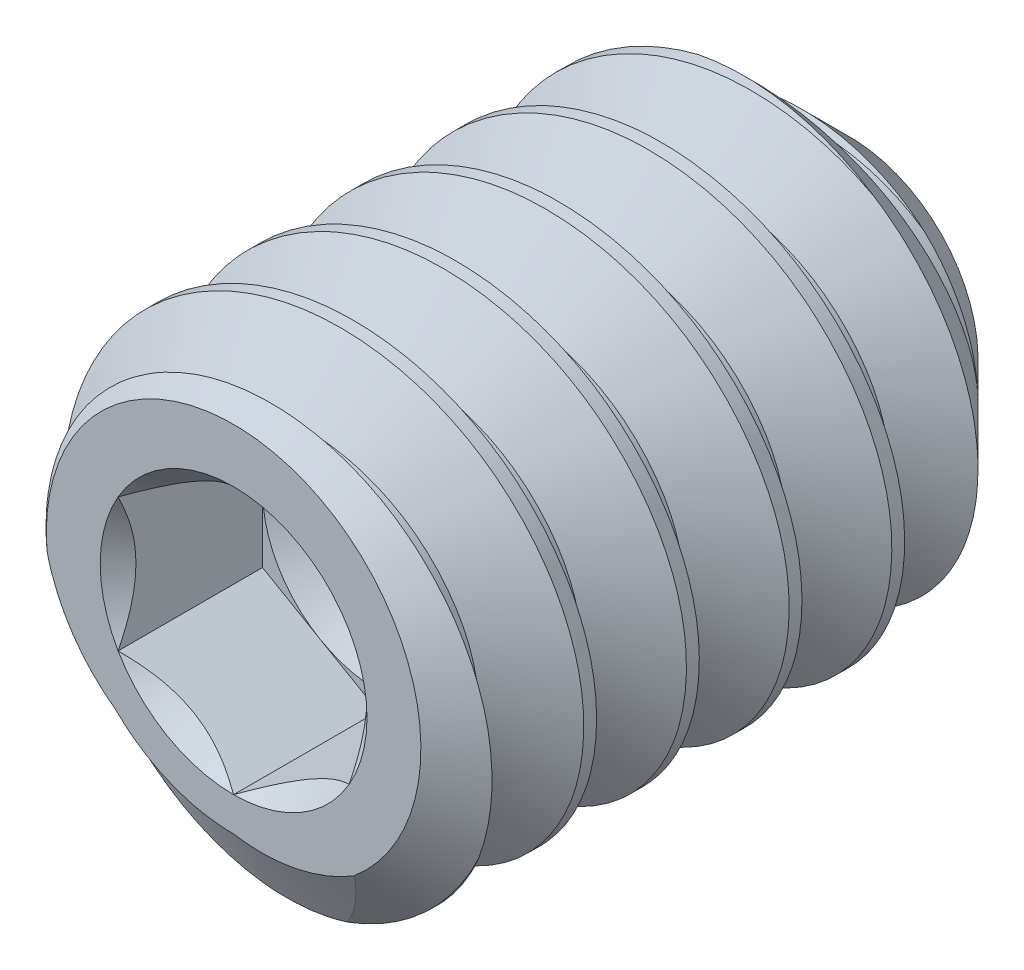
SolidWorks part; units mm, degrees
ref_plane "Front" through (0, 0, 0) normal (0, 0, 1) x (1, 0, 0)
ref_plane "Top" through (0, 0, 0) normal (0, 1, 0) x (1, 0, 0)
ref_plane "Right" through (0, 0, 0) normal (1, 0, 0) x (0, 0, -1)
sketch "Sketch22" plane through (0, 0, 0) normal (1, 0, 0) x (0, 0, -1)
  line L0 (-2.7778, 0) -> (-2.7778, 1.9304)
  line L1 (-2.7778, 1.9304) -> (-2.4398, 2.413)
  line L2 (-2.4398, 2.413) -> (2.4815, 2.413)
  line L3 (2.4815, 2.413) -> (3.5722, 1.3222)
  line L4 (3.5722, 1.3222) -> (2.7778, 0) construction
  line L5 (2.7778, 0) -> (-2.7778, 0)
  line L6 (2.7778, 0) -> (3.5722, 0) construction
  line L7 (3.5722, 0) -> (3.5722, 1.3222) construction
  line L8 (3.5722, -1.3222) -> (2.7778, 0) construction
  line L9 (-2.4398, -2.413) -> (2.4815, -2.413) construction
  line L10 (3.5722, 1.3222) -> (3.5722, 0)
  line L11 (3.5722, 0) -> (2.7778, 0)
  dimension "Dia" = 4.826
  dimension "Length" = 6.35
  dimension "D3" = 35
  dimension "D5" = 118
  dimension "D6" = 45
  dimension "D7" = 3.8608
revolve "Revolve1" add sketch "Sketch22" angle 360 about L6
ref_plane "Plane1" through (0, 0, -3.5722) normal (0, 0, 1) x (1, 0, 0)
sketch "Sketch27" plane through (0, 0, -3.5722) normal (0, 0, 1) x (1, 0, 0)
  circle A0 centre (0, 0) radius 2.413 construction
  circle A1 centre (0, 0) radius 2.413
curve "Helix/Spiral1" pitch 1.0583 height 7.4083 radius 2.413 centre (0, 0, -3.5722) axis (0, 0, 1) start towards (0, 1, 0)
sketch "Sketch28" plane through (0, 0, 0) normal (1, 0, 0) x (0, 0, -1)
  line L0 (3.5722, 2.413) -> (4.4983, 2.413)
  line L1 (4.4983, 2.413) -> (4.1014, 1.7256)
  line L2 (4.1014, 1.7256) -> (3.9691, 1.7256)
  line L3 (3.9691, 1.7256) -> (3.5722, 2.413)
  line L4 (3.7707, 2.0693) -> (4.2998, 2.0693) construction
  line L6 (-2.4398, 2.413) -> (2.4815, 2.413) construction
  line L7 (3.5722, 6.985) -> (3.5722, -6.985) construction
  dimension "D1" = 0.1323
  dimension "D3" = 60
  dimension "D2" = 0.5292
sweep "Cut-Sweep2" cut profiles "Sketch28" path "Helix/Spiral1" align with end faces yes
sketch "Sketch23" plane through (0, 0, 2.7778) normal (0, 0, 1) x (1, 0, 0)
  line L1 (0, 1.3748) -> (-1.1906, 0.6874)
  line L2 (-1.1906, 0.6874) -> (-1.1906, -0.6874)
  line L3 (-1.1906, -0.6874) -> (0, -1.3748)
  line L4 (0, -1.3748) -> (1.1906, -0.6874)
  line L5 (1.1906, -0.6874) -> (1.1906, 0.6874)
  line L6 (1.1906, 0.6874) -> (0, 1.3748)
  circle A0 centre (0, 0) radius 1.1906 construction
  dimension "Hex" = 2.3813
extrude "Cut-Extrude10" cut sketch "Sketch23" against normal blind 1.4883
sketch "Sketch24" plane through (0, 0, 2.7778) normal (0, 0, 1) x (1, 0, 0)
  circle A0 centre (0, 0) radius 1.3748
extrude "Cut-Extrude11" cut sketch "Sketch24" against normal through all draft 45
sketch "Sketch26" plane through (0, 0, 1.2895) normal (0, 0, 1) x (1, 0, 0)
  circle A0 centre (0, 0) radius 1.1906 construction
  circle A1 centre (0, 0) radius 1.1906
extrude "Cut-Extrude12" cut sketch "Sketch26" against normal through all draft 60
sketch "Sketch30" plane through (0, 0, 0) normal (1, 0, 0) x (0, 0, -1)
  line L0 (-2.4398, 2.413) -> (2.4815, 2.413) construction
  line L1 (-2.7778, 0) -> (-2.7778, 1.9304) construction
  line L2 (3.5722, 0) -> (3.5722, 1.3222) construction
  line L3 (-2.4398, -2.413) -> (2.4815, -2.413) construction
  point P0 (-2.7778, 2.413)
  point P1 (3.5722, 2.413)
  point P2 (3.5722, -2.413)
  point P11 (-0.1319, -2.413)
  dimension "D1" = 3.7042
sketch "Sketch31" plane through (0, 0, 0) normal (1, 0, 0) x (0, 0, -1)
  line L2 (2.7778, 0) -> (3.5722, -1.3222)
  line L3 (3.5722, 1.3222) -> (2.7778, 0)
equation "\"D7@Sketch22\"=\"Dia@Sketch22\"*.8"
equation "\"D1@Sketch28\" = \"D4@Helix/Spiral1\" * .125"
equation "\"D3@Helix/Spiral1\" = \"Length@Sketch22\" + \"D4@Helix/Spiral1\""
equation "\"D1@Sketch30\" = \"D4@Helix/Spiral1\" * 3.5"
equation "\"hex Depth@Cut-Extrude10\" = \"Hex@Sketch23\" * .625"
equation "\"D2@Sketch28\" = \"D4@Helix/Spiral1\" * .5"
